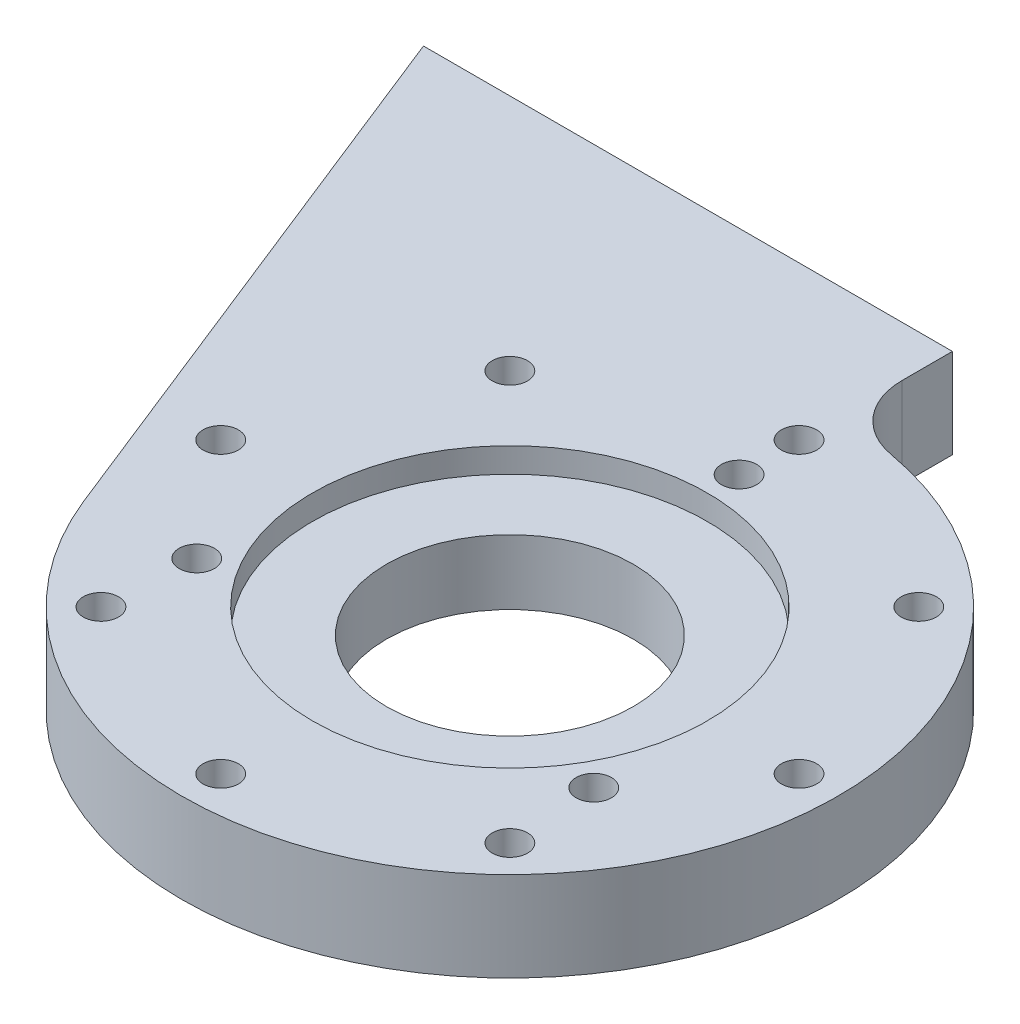
SolidWorks part; units mm, degrees
ref_plane "Front Plane" through (0, 0, 0) normal (0, 0, 1) x (1, 0, 0)
ref_plane "Top Plane" through (0, 0, 0) normal (0, 1, 0) x (1, 0, 0)
ref_plane "Right Plane" through (0, 0, 0) normal (1, 0, 0) x (0, 0, -1)
sketch "Sketch1" plane through (0, 0, 0) normal (0, 1, 0) x (1, 0, 0)
  circle A0 centre (0, 0) radius 46.5
  circle A1 centre (0, 0) radius 32.5 construction
  circle A2 centre (0, 32.5) radius 2.5
  circle A3 centre (28.1458, -16.25) radius 2.5
  circle A4 centre (-28.1458, -16.25) radius 2.5
  circle A5 centre (0, 0) radius 17.5
  point P13 (0, 0)
  dimension "D1" = 93
  dimension "D2" = 65
  dimension "D3" = 5
  dimension "D5" = 35
  dimension "D4" = 3
extrude "Boss-Extrude1" add sketch "Sketch1" along normal blind 12.7
sketch "Sketch2" plane through (0, 12.7, 0) normal (0, 1, 0) x (1, 0, 0)
  circle A0 centre (0, 0) radius 28
  dimension "D1" = 56
extrude "Cut-Extrude1" cut sketch "Sketch2" against normal blind 3.5
sketch "Sketch3" plane through (0, 12.7, 0) normal (0, 1, 0) x (1, 0, 0)
  line L0 (0, 41) -> (0, 0) construction
  circle A0 centre (0, 0) radius 41 construction
  circle A1 centre (0, 41) radius 2.5
  circle A2 centre (28.9914, 28.9914) radius 2.5
  circle A3 centre (41, 0) radius 2.5
  circle A4 centre (28.9914, -28.9914) radius 2.5
  circle A5 centre (0, -41) radius 2.5
  circle A6 centre (-28.9914, -28.9914) radius 2.5
  circle A7 centre (-41, 0) radius 2.5
  circle A8 centre (-28.9914, 28.9914) radius 2.5
  point P6 (0, 0)
  point P7 (0, 0)
  point P21 (0, 0)
  dimension "D1" = 82
  dimension "D2" = 5
  dimension "D3" = 8
extrude "Cut-Extrude2" cut sketch "Sketch3" against normal blind 8
sketch "Sketch4" plane through (0, 0, 0) normal (0, -1, 0) x (1, 0, 0)
  line L0 (-43.208, 17.1849) -> (-75, -62.75)
  line L1 (-75, -62.75) -> (0, -62.75)
  line L3 (0, -62.75) -> (0, -46.5)
  circle A0 centre (0, 0) radius 46.5 construction
  circle A1 centre (0, 0) radius 46.5
  arc A2 (-43.208, 17.1849) -> (0, -46.5) centre (0, 0) ccw
  point P4 (-38.3802, 26.2528)
  dimension "D2" = 62.75
  dimension "D3" = 75
  dimension "D1" = 0
extrude "Boss-Extrude2" add sketch "Sketch4" against normal up to surface (12.7 mm away) up to face at (0, 12.7, -38.5)
fillet "Fillet1" radius 10 1 edges at (0, 6.35, -46.5)
